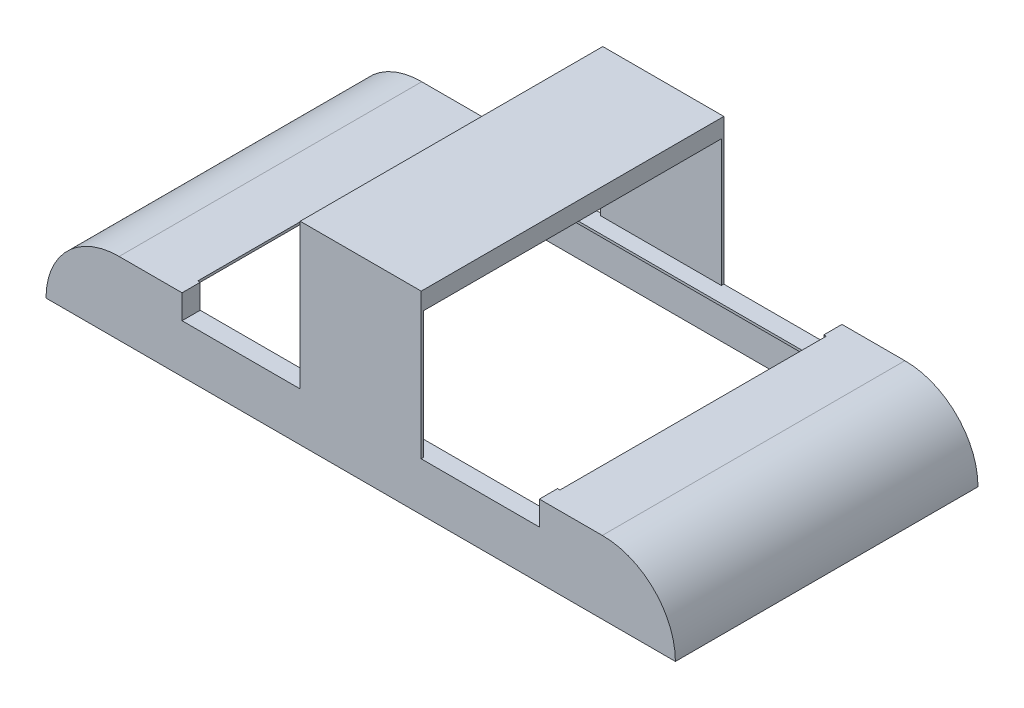
SolidWorks part; units mm, degrees
ref_plane "Front Plane" through (0, 0, 0) normal (0, 0, 1) x (1, 0, 0)
ref_plane "Top Plane" through (0, 0, 0) normal (0, 1, 0) x (1, 0, 0)
ref_plane "Right Plane" through (0, 0, 0) normal (1, 0, 0) x (0, 0, -1)
sketch "Sketch1" plane through (0, 0, 0) normal (0, 0, 1) x (1, 0, 0)
  line L0 (0, 0) -> (520, 0)
  line L1 (459.6027, 60) -> (60.3973, 60)
  line L2 (260, 60) -> (260, -13.9535) construction
  arc A0 (520, 0) -> (459.6027, 60) centre (459.9987, 0) ccw
  arc A1 (0, 0) -> (60.3973, 60) centre (60.0013, 0) cw
  point P9 (60.0013, 60)
  dimension "D3" = 60.0013
  dimension "D1" = 520
  dimension "D2" = 60
extrude "Boss-Extrude1" add sketch "Sketch1" along normal blind 250
sketch "Sketch2" plane through (0, 60, 0) normal (0, 1, 0) x (1, 0, 0)
  line L0 (459.6027, 0) -> (60.3973, 0) construction
  line L1 (110.3973, -15) -> (409.6027, -15)
  line L2 (110.3973, -15) -> (110.3973, -235)
  line L3 (110.3973, -235) -> (409.6027, -235)
  line L4 (409.6027, -15) -> (409.6027, -235)
  line L5 (459.6027, -250) -> (60.3973, -250) construction
  line L6 (60.3973, -250) -> (60.3973, 0) construction
  line L7 (459.6027, -250) -> (459.6027, 0) construction
  dimension "D1" = 15
  dimension "D2" = 15
  dimension "D3" = 50
  dimension "D4" = 50
extrude "Cut-Extrude1" cut sketch "Sketch2" against normal through all
sketch "Sketch4" plane through (0, 60, 0) normal (0, 1, 0) x (1, 0, 0)
  line L0 (459.6027, -250) -> (60.3973, -250) construction
  line L1 (110.3973, -235) -> (409.6027, -235)
  line L2 (110.3973, -235) -> (110.3973, -250)
  line L3 (110.3973, -250) -> (409.6027, -250)
  line L4 (409.6027, -235) -> (409.6027, -250)
  line L5 (459.6027, 0) -> (60.3973, 0) construction
  line L6 (409.6027, -15) -> (110.3973, -15)
  line L7 (409.6027, -15) -> (409.6027, 0)
  line L8 (409.6027, 0) -> (110.3973, 0)
  line L9 (110.3973, -15) -> (110.3973, 0)
  point P14 (0, 0)
extrude "Cut-Extrude2" cut sketch "Sketch4" against normal blind 20
shell "Shell1" thickness 2 removed face at (260, 0, 125) removed face at (260, 20, 15) removed face at (409.6027, 35, 125) removed face at (260, 20, 235) removed face at (110.3973, 35, 125)
sketch "Sketch5" plane through (409.6027, 0, 0) normal (-1, 0, 0) x (0, 0, 1)
  line L0 (15, 40) -> (2, 40) construction
  line L1 (0, 60) -> (15, 60)
  line L2 (0, 60) -> (0, 40)
  line L3 (0, 40) -> (15, 40)
  line L4 (15, 60) -> (15, 40)
  line L5 (248, 40) -> (235, 40) construction
  line L6 (250, 60) -> (235, 60)
  line L7 (250, 60) -> (250, 40)
  line L8 (250, 40) -> (235, 40)
  line L9 (235, 60) -> (235, 40)
  dimension "D1" = 15
  dimension "D2" = 15
extrude "Boss-Extrude2" add sketch "Sketch5" along normal blind 2
sketch "Sketch6" plane through (110.3973, 0, 0) normal (1, 0, 0) x (0, 0, -1)
  line L2 (-250, 60) -> (-235, 60)
  line L3 (-250, 60) -> (-250, 40)
  line L4 (-250, 40) -> (-235, 40)
  line L5 (-235, 60) -> (-235, 40)
  line L6 (-15, 40) -> (0, 40)
  line L7 (-15, 40) -> (-15, 60)
  line L8 (-15, 60) -> (0, 60)
  line L9 (0, 40) -> (0, 60)
extrude "Boss-Extrude3" add sketch "Sketch6" along normal blind 2
sketch "Sketch7" plane through (0, 0, 250) normal (0, 0, 1) x (1, 0, 0)
  line L0 (210, 40) -> (210, 160)
  line L1 (112.3973, 40) -> (407.6027, 40) construction
  line L2 (210, 160) -> (310, 160)
  line L3 (310, 160) -> (310, 40)
  line L4 (260, 40) -> (260, 214.0731) construction
  line L5 (210, 40) -> (310, 40)
  dimension "D1" = 50
  dimension "D2" = 50
  dimension "D3" = 120
extrude "Boss-Extrude4" add sketch "Sketch7" against normal blind 250
sketch "Sketch8" plane through (310, 0, 0) normal (1, 0, 0) x (0, 0, -1)
  line L0 (0, 160) -> (-250, 160) construction
  line L1 (-248, 145) -> (-2, 145)
  line L2 (-248, 145) -> (-248, 40)
  line L4 (-2, 145) -> (-2, 40)
  line L5 (-250, 40) -> (-250, 160) construction
  line L6 (0, 40) -> (0, 160) construction
  line L8 (-15, 40) -> (-235, 40) construction
  line L9 (-15, 40) -> (-235, 40)
  line L11 (-235, 40) -> (-250, 40) construction
  line L12 (0, 40) -> (-15, 40) construction
  line L13 (-235, 40) -> (-248, 40)
  line L14 (-15, 40) -> (-2, 40)
  dimension "D1" = 15
  dimension "D2" = 2
  dimension "D3" = 2
extrude "Cut-Extrude3" cut sketch "Sketch8" against normal blind 100
